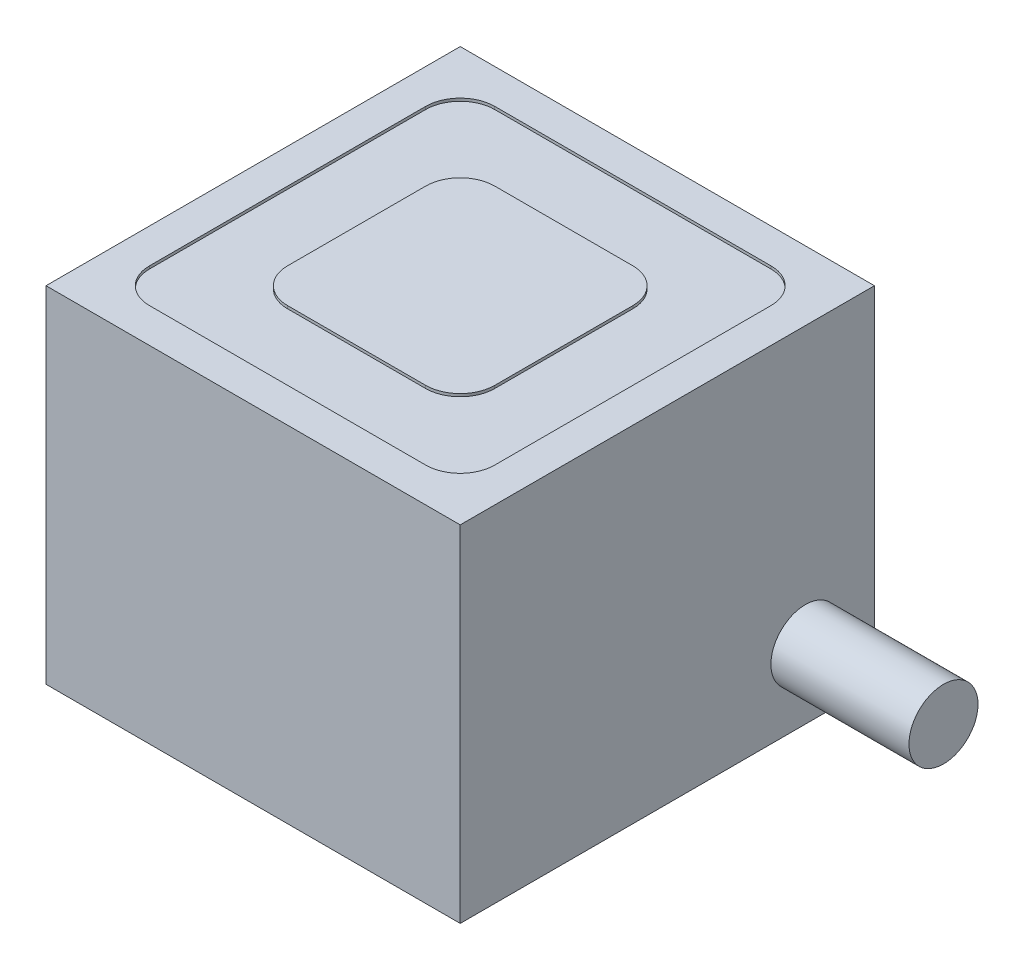
SolidWorks part; units mm, degrees
ref_plane "Front Plane" through (0, 0, 0) normal (0, 0, 1) x (1, 0, 0)
ref_plane "Top Plane" through (0, 0, 0) normal (0, 1, 0) x (1, 0, 0)
ref_plane "Right Plane" through (0, 0, 0) normal (1, 0, 0) x (0, 0, -1)
sketch "Sketch1" plane through (0, 0, 0) normal (0, 1, 0) x (1, 0, 0)
  line L1 (0, -19.05) -> (38.1, -19.05)
  line L2 (0, -19.05) -> (0, 19.05)
  line L3 (0, 19.05) -> (38.1, 19.05)
  line L4 (38.1, -19.05) -> (38.1, 19.05)
  circle A0 centre (0, 0) radius 25.4 construction
  dimension "A" = 50.8
  dimension "Wd." = 38.1
  dimension "Lg." = 38.1
extrude "Boss-Extrude1" add sketch "Sketch1" along normal blind 31.75
sketch "Sketch2" plane through (0, 31.75, 0) normal (0, 1, 0) x (1, 0, 0)
  line L0 (3.175, 0) -> (0, 0) construction
  line L1 (12.7, 9.525) -> (25.4, 9.525)
  line L2 (9.525, 6.35) -> (9.525, -6.35)
  line L3 (12.7, -9.525) -> (25.4, -9.525)
  line L4 (28.575, 6.35) -> (28.575, -6.35)
  line L5 (6.35, 15.875) -> (31.75, 15.875)
  line L6 (3.175, 12.7) -> (3.175, -12.7)
  line L7 (6.35, -15.875) -> (31.75, -15.875)
  line L8 (34.925, 12.7) -> (34.925, -12.7)
  line L9 (3.175, 0) -> (9.525, 0) construction
  line L10 (9.525, 0) -> (28.575, 0) construction
  line L11 (28.575, 0) -> (34.925, 0) construction
  line L12 (34.925, 0) -> (38.1, 0) construction
  line L13 (38.1, -19.05) -> (38.1, 19.05) construction
  line L14 (19.05, 19.05) -> (19.05, 15.875) construction
  line L15 (38.1, 19.05) -> (0, 19.05) construction
  line L16 (19.05, 15.875) -> (19.05, 9.525) construction
  line L17 (19.05, 9.525) -> (19.05, -9.525) construction
  line L18 (19.05, -9.525) -> (19.05, -15.875) construction
  line L19 (19.05, -15.875) -> (19.05, -19.05) construction
  line L20 (0, -19.05) -> (38.1, -19.05) construction
  arc A0 (25.4, 9.525) -> (28.575, 6.35) centre (25.4, 6.35) cw
  arc A1 (25.4, -9.525) -> (28.575, -6.35) centre (25.4, -6.35) ccw
  arc A2 (9.525, -6.35) -> (12.7, -9.525) centre (12.7, -6.35) ccw
  arc A3 (12.7, 9.525) -> (9.525, 6.35) centre (12.7, 6.35) ccw
  arc A4 (31.75, 15.875) -> (34.925, 12.7) centre (31.75, 12.7) cw
  arc A5 (31.75, -15.875) -> (34.925, -12.7) centre (31.75, -12.7) ccw
  arc A6 (3.175, -12.7) -> (6.35, -15.875) centre (6.35, -12.7) ccw
  arc A7 (6.35, 15.875) -> (3.175, 12.7) centre (6.35, 12.7) ccw
  dimension "D3" = 3.175
  dimension "D4" = 3.175
  dimension "D1" = 3.175
  dimension "D2" = 6.35
extrude "Cut-Extrude0" cut sketch "Sketch2" against normal blind 0.254
sketch "Sketch3" plane through (0, 0, 0) normal (0, -1, 0) x (1, 0, 0)
  line L0 (0, 0) -> (19.05, 0) construction
  circle A0 centre (19.05, 0) radius 2.413
  circle A1 centre (19.05, 0) radius 2.413 construction
  point P3 (16.637, 0)
  point P4 (21.463, 0)
  point P5 (19.05, 0)
  point P10 (16.637, 0)
  point P11 (21.463, 0)
  dimension "Hole Dia." = 4.826
  dimension "CtoC" = 0
  dimension "L1" = 19.05
extrude "Cut-Extrude1" cut sketch "Sketch3" against normal blind 9.525
sketch "Sketch4" plane through (0, 0, 0) normal (0, -1, 0) x (1, 0, 0)
  circle A1 centre (19.05, 0) radius 2.413
  circle A2 centre (19.05, 0) radius 2.413
  point P0 (16.637, 0)
  dimension "D1" = 0
curve "Helix/Spiral1" pitch 0.7937 height 10.3188 turns 13 parameters "Pitch"=0.7937
sketch "Sketch5" plane through (0, 0, 0) normal (0, 0, 1) x (1, 0, 0)
  line L0 (16.5511, 0.0496) -> (16.5511, -0.7441) construction
  line L1 (16.5511, -0.7441) -> (17.2385, -0.3473) construction
  line L2 (17.2385, -0.3473) -> (16.5511, 0.0496) construction
  line L3 (16.637, 0) -> (16.637, -0.6945) construction
  line L4 (17.1526, -0.2977) -> (17.1526, -0.3969) construction
  line L5 (17.2385, -0.3473) -> (17.1526, -0.3473) construction
  line L6 (17.1526, -0.3473) -> (17.0666, -0.3473) construction
  line L7 (16.637, -0.3473) -> (16.5511, -0.3473) construction
  line L8 (16.594, -0.7193) -> (16.594, 0.0248)
  line L9 (16.594, 0.0248) -> (17.0666, -0.248)
  line L10 (17.0666, -0.248) -> (17.0666, -0.4465)
  line L11 (17.0666, -0.4465) -> (16.594, -0.7193)
  point P16 (16.594, -0.3473)
  dimension "D1" = 0.7937
  dimension "D2" = 0.0992
sketch "Sketch6" plane through (0, 0, 0) normal (0, -1, 0) x (1, 0, 0)
  circle A0 centre (19.05, 0) radius 2.4989
sweep "Sweep1" add profiles "Sketch5" path "Helix/Spiral1"
extrude "Cut-Extrude2" cut sketch "Sketch6" against normal through all draft 45 and the other way through all
sketch "Sketch7" plane through (0, 0, 0) normal (1, 0, 0) x (0, 0, -1)
  line L0 (12.7, 6.35) -> (12.7, 0) construction
  line L1 (-19.05, 31.75) -> (-19.05, 0) construction
  line L2 (-19.05, 0) -> (19.05, 0) construction
  circle A0 centre (12.7, 6.35) radius 3.175
  dimension "Wire Dia." = 6.35
  dimension "B" = 31.75
  dimension "C" = 6.35
pattern_linear "LPattern1" [suppressed] count 2 spacing 25.4 along (1, 0, 0)
sketch "Sketch8" plane through (0, 0, 0) normal (0, 0, 1) x (1, 0, 0)
  line L0 (0, 6.35) -> (50.8, 6.35) construction
  line L2 (38.1, 31.75) -> (38.1, 0) construction
  dimension "D1" = 12.7
extrude "Boss-Extrude2" add sketch "Sketch7" against normal up to surface (12.7 mm away) from vertex at 50.8 up to face at (38.1, 15.875, 0) starting at point (50.8, 6.35, 0)
sketch "Sketch9" plane through (0, 0, 0) normal (0, 0, 1) x (1, 0, 0)
  line L0 (16.637, 0) -> (16.637, 9.525) construction
  line L1 (16.637, 9.525) -> (21.463, 9.525) construction
  line L2 (21.463, 9.525) -> (21.463, 0) construction
  line L3 (16.637, 9.525) -> (19.809, 9.525) construction
  line L4 (16.637, 0) -> (16.637, 9.525) construction
  line L5 (21.463, 0) -> (21.463, 9.525) construction
  line L6 (21.463, 9.525) -> (16.637, 9.525) construction
equation "\"D3@Helix/Spiral1\" = \"Pitch@Helix/Spiral1\" + \"Hole Depth@Cut-Extrude1\""
equation "\"D1@Sketch5\" = \"Pitch@Helix/Spiral1\""
equation "\"D2@Sketch5\" = \"D1@Sketch5\" / 8"
equation "\"D3@LPattern1\" = \"CtoC@Sketch3\""
